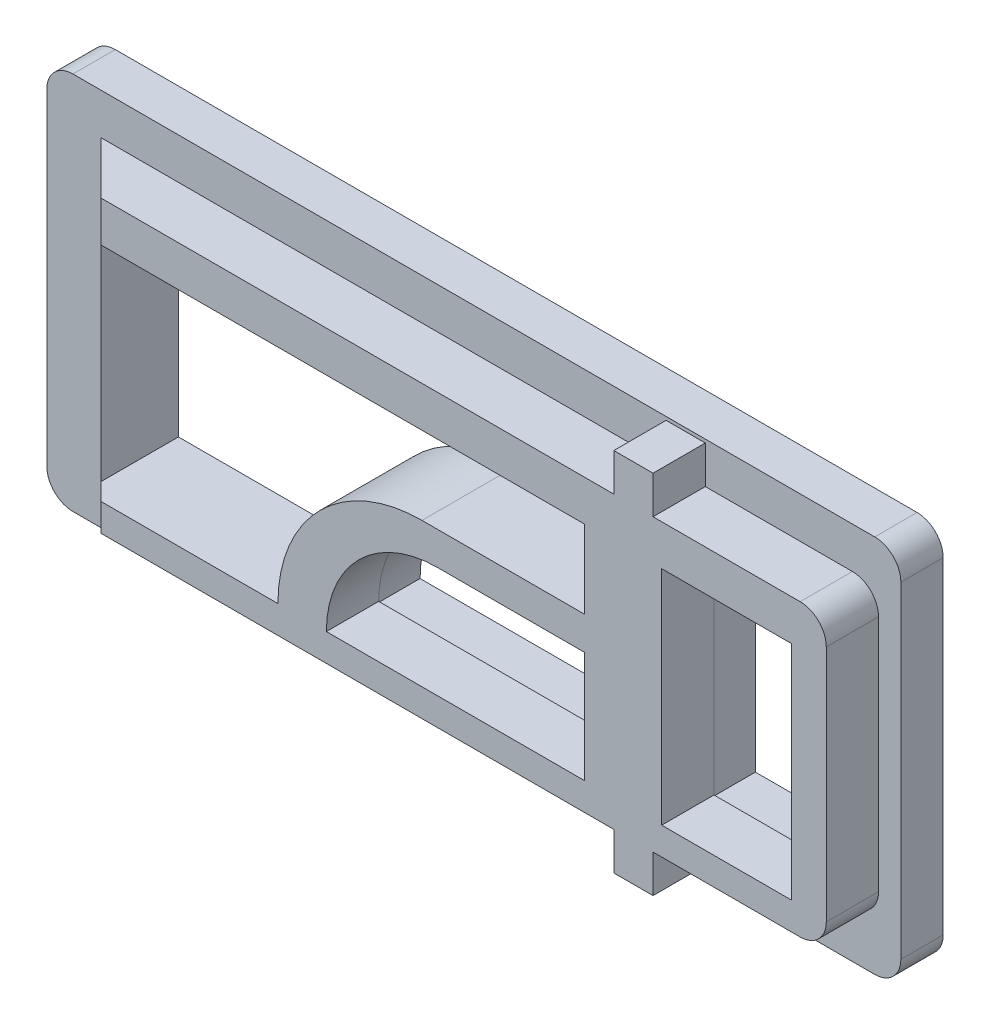
SolidWorks part; units mm, degrees
ref_plane "Alzado" through (0, 0, 0) normal (0, 0, 1) x (1, 0, 0)
ref_plane "Planta" through (0, 0, 0) normal (0, 1, 0) x (1, 0, 0)
ref_plane "Vista lateral" through (0, 0, 0) normal (1, 0, 0) x (0, 0, -1)
sketch "Sketch1" plane through (0, 0, 0) normal (0, 0, 1) x (1, 0, 0)
  line L5 (-16.34, 7.25) -> (16.34, 7.25)
  line L6 (-16.34, 7.25) -> (-16.34, -7.25)
  line L7 (-16.34, -7.25) -> (16.34, -7.25)
  line L9 (16.34, 7.25) -> (16.34, -7.25)
  line L10 (-16.34, 7.25) -> (16.34, -7.25) construction
  line L12 (-16.34, -7.25) -> (16.34, 7.25) construction
  point P0 (0, 0)
  point P6 (-5.1624, 7.25)
  dimension "D1" = 32.68
  dimension "D2" = 14.5
extrude "Boss-Extrude2" add sketch "Sketch1" against normal blind 1.62
sketch "Sketch3" plane through (0, 0, 0) normal (0, 0, 1) x (1, 0, 0)
  line L0 (-16.3228, 5.6764) -> (7.3572, 5.6764)
  line L1 (16.3572, -6.8795) -> (-16.3228, -6.8795)
  line L2 (16.3572, -6.8795) -> (16.3572, 7.1205)
  line L3 (16.3572, 7.1205) -> (-16.3228, 7.1205)
  line L4 (-16.3228, -6.8795) -> (-16.3228, 7.1205)
  line L5 (16.3572, -6.8795) -> (-16.3228, 7.1205) construction
  line L6 (16.3572, 7.1205) -> (-16.3228, -6.8795) construction
  line L7 (7.3572, 5.6764) -> (7.3572, 7.1205)
  line L8 (7.3572, 7.1205) -> (8.8572, 7.1205)
  line L9 (8.8572, 7.1205) -> (8.8572, 5.6764)
  line L10 (8.8572, 5.6764) -> (15.4865, 5.6764)
  line L11 (8.8572, -5.4353) -> (15.4865, -5.4353)
  line L12 (8.8572, -6.8795) -> (8.8572, -5.4353)
  line L13 (7.3572, -5.4353) -> (7.3572, -6.8795)
  line L14 (-16.3228, -5.4353) -> (7.3572, -5.4353)
  line L15 (8.8572, -6.8795) -> (7.3572, -6.8795)
  line L16 (-14.5652, 5.6764) -> (-14.5652, -5.4353)
  line L17 (6.2319, -4.3789) -> (-3.6428, -4.3789)
  line L18 (14.1512, -4.3789) -> (9.1889, -4.3789)
  line L19 (14.1512, -4.3789) -> (14.1512, 4.1211)
  line L20 (14.1512, 4.1211) -> (9.1889, 4.1211)
  line L21 (9.1889, -4.3789) -> (9.1889, 4.1211)
  line L22 (14.1512, -4.3789) -> (9.1889, 4.1211) construction
  line L23 (14.1512, 4.1211) -> (9.1889, -4.3789) construction
  line L24 (0.6072, -0.1289) -> (6.2319, -0.1289)
  line L25 (6.2319, -0.1289) -> (6.2319, -4.3789)
  line L26 (6.2319, 2.506) -> (6.2319, 4.1211)
  line L27 (6.2319, 4.1211) -> (-12.924, 4.1211)
  line L28 (-12.924, 4.1211) -> (-12.924, -4.3789)
  line L29 (-12.924, -4.3789) -> (-5.497, -4.3789)
  line L30 (0.0172, 1.1353) -> (6.2319, 1.1353)
  line L31 (6.2319, 1.1353) -> (6.2319, 2.506)
  line L32 (7.3572, -6.8795) -> (8.8572, -6.8795)
  line L33 (7.3572, 7.1205) -> (8.8572, 7.1205)
  line L34 (16.3572, 4.8057) -> (16.3572, -4.5646)
  line L35 (-16.3228, -5.4353) -> (-16.3228, 5.6764)
  line L36 (7.3572, 5.6764) -> (8.8572, 5.6764)
  line L37 (7.3572, -5.4353) -> (8.8572, -5.4353)
  line L38 (15.4865, 5.6764) -> (15.4865, -5.4353)
  arc A0 (15.4865, 5.6764) -> (16.3572, 4.8057) centre (15.4865, 4.8057) cw
  arc A1 (15.4865, -5.4353) -> (16.3572, -4.5646) centre (15.4865, -4.5646) ccw
  arc A2 (-3.6428, -4.3789) -> (0.6072, -0.1289) centre (0.6072, -4.3789) cw
  arc A3 (-5.497, -4.3789) -> (0.0172, 1.1353) centre (0.0172, -4.3789) cw
  point P0 (0.0172, 0.1205)
  point P23 (11.6701, -0.1289)
  dimension "D5" = 4.25
  dimension "D1" = 14
  dimension "D2" = 32.68
  dimension "D3" = 1.5
  dimension "D4" = 4.25
  dimension "D6" = 7.5
  dimension "D7" = 15.75
  dimension "D8" = 4.25
extrude "Boss-Extrude3" add sketch "Sketch3" along normal blind 2 contours L38 L10 L36 L0 L16 L14 L37 L11 A3 L29 L28 L27 L26 L31 L30 L18 L21 L20 L19 L17 A2 L24 L25 | L37 L13 L1 L12 | L7 L36 L9 L3 region at (1.297, 0.3545, 0) region at (8.1072, 6.3985, 0) region at (8.1072, -6.1574, 0)
sketch "Sketch4" plane through (0, 0, 0) normal (0, 0, 1) x (1, 0, 0)
  line L0 (-16.3572, 5.6075) -> (7.3228, 5.6075)
  line L1 (16.3228, -6.9483) -> (-16.3572, -6.9483)
  line L2 (16.3228, -6.9483) -> (16.3228, 7.0517)
  line L3 (16.3228, 7.0517) -> (-16.3572, 7.0517)
  line L4 (-16.3572, -6.9483) -> (-16.3572, 7.0517)
  line L5 (16.3228, -6.9483) -> (-16.3572, 7.0517) construction
  line L6 (16.3228, 7.0517) -> (-16.3572, -6.9483) construction
  line L7 (7.3228, 5.6075) -> (7.3228, 7.0517)
  line L8 (7.3228, 7.0517) -> (8.8228, 7.0517)
  line L9 (8.8228, 7.0517) -> (8.8228, 5.6075)
  line L10 (8.8228, 5.6075) -> (15.4521, 5.6075)
  line L11 (8.8228, -5.5042) -> (15.4521, -5.5042)
  line L12 (8.8228, -6.9483) -> (8.8228, -5.5042)
  line L13 (7.3228, -5.5042) -> (7.3228, -6.9483)
  line L14 (-16.3572, -5.5042) -> (7.3228, -5.5042)
  line L15 (8.8228, -6.9483) -> (7.3228, -6.9483)
  line L16 (-14.5997, 5.6075) -> (-14.5997, -5.5042)
  line L17 (6.1975, -4.4477) -> (-3.6772, -4.4477)
  line L18 (14.1168, -4.4477) -> (9.1545, -4.4477)
  line L19 (14.1168, -4.4477) -> (14.1168, 4.0523)
  line L20 (14.1168, 4.0523) -> (9.1545, 4.0523)
  line L21 (9.1545, -4.4477) -> (9.1545, 4.0523)
  line L22 (14.1168, -4.4477) -> (9.1545, 4.0523) construction
  line L23 (14.1168, 4.0523) -> (9.1545, -4.4477) construction
  line L24 (0.5728, -0.1977) -> (6.1975, -0.1977)
  line L25 (6.1975, -0.1977) -> (6.1975, -4.4477)
  line L26 (6.1975, 2.4372) -> (6.1975, 4.0523)
  line L27 (6.1975, 4.0523) -> (-12.9584, 4.0523)
  line L28 (-12.9584, 4.0523) -> (-12.9584, -4.4477)
  line L29 (-12.9584, -4.4477) -> (-5.5314, -4.4477)
  line L30 (-0.0172, 1.0664) -> (6.1975, 1.0664)
  line L31 (6.1975, 1.0664) -> (6.1975, 2.4372)
  line L32 (7.3228, -6.9483) -> (8.8228, -6.9483)
  line L33 (7.3228, 7.0517) -> (8.8228, 7.0517)
  line L34 (16.3228, 4.7368) -> (16.3228, -4.6335)
  line L35 (-16.3572, -5.5042) -> (-16.3572, 5.6075)
  line L36 (7.3228, 5.6075) -> (8.8228, 5.6075)
  line L37 (7.3228, -5.5042) -> (8.8228, -5.5042)
  line L38 (15.4521, 5.6075) -> (15.4521, -5.5042)
  arc A0 (15.4521, 5.6075) -> (16.3228, 4.7368) centre (15.4521, 4.7368) cw
  arc A1 (15.4521, -5.5042) -> (16.3228, -4.6335) centre (15.4521, -4.6335) ccw
  arc A2 (-3.6772, -4.4477) -> (0.5728, -0.1977) centre (0.5728, -4.4477) cw
  arc A3 (-5.5314, -4.4477) -> (-0.0172, 1.0664) centre (-0.0172, -4.4477) cw
  point P0 (-0.0172, 0.0517)
  point P23 (11.6356, -0.1977)
  line M12 (-12.924, -4.3789) -> (-5.497, -4.3789)
  arc M13 (-5.497, -4.3789) -> (0.0172, 1.1353) centre (0.0172, -4.3789) cw
  line M14 (0.0172, 1.1353) -> (6.2319, 1.1353)
  line M17 (-12.924, 4.1211) -> (-12.924, -4.3789)
  dimension "D5" = 4.25
  dimension "D1" = 14
  dimension "D2" = 32.68
  dimension "D3" = 1.5
  dimension "D4" = 4.25
  dimension "D6" = 7.5
  dimension "D7" = 15.75
  dimension "D8" = 4.25
extrude "Cut-Extrude1" cut sketch "Sketch4" against normal blind 2 contours A3 L31 L26 L27 M12 M13 M14 M17 | A2 L17 L25 L24 | L21 L18 L19 L20 region at (1.666, -2.4424, 0) region at (11.6356, -0.1977, 0) region at (-5.7395, 0.7536, 0)
fillet "Fillet1" radius 1 6 edges at (15.4865, -5.4353, 1) (15.4865, 5.6764, 1) (16.34, 7.25, -0.81) (16.34, -7.25, -0.81) (-16.34, -7.25, -0.81) (-16.34, 7.25, -0.81)
chamfer "Chamfer1" distance 2.3 angle 45 1 edges at (-14.5652, 0.1205, 2)
